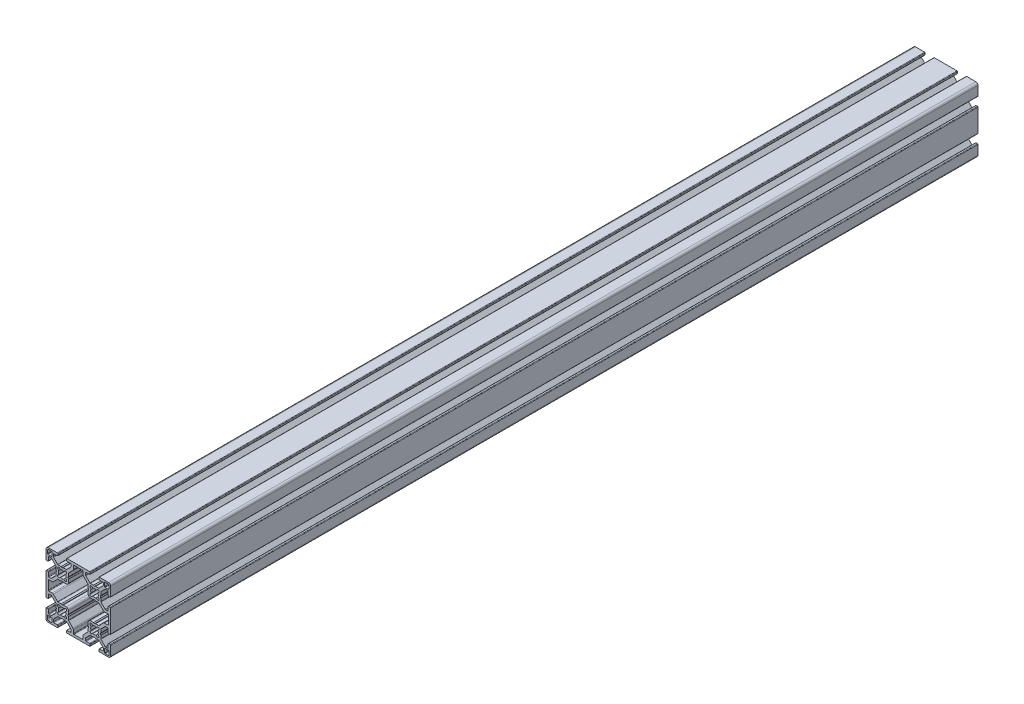
SolidWorks part; units mm, degrees
material "6105-T5 Aluminum"
ref_plane "Front Plane" through (0, 0, 0) normal (0, 0, 1) x (1, 0, 0)
ref_plane "Top Plane" through (0, 0, 0) normal (0, 1, 0) x (1, 0, 0)
ref_plane "Right Plane" through (0, 0, 0) normal (1, 0, 0) x (0, 0, -1)
sketch "Sketch1" plane through (0, 0, 0) normal (0, 0, 1) x (1, 0, 0)
  line L0 (-13.319, -39.4999) -> (-9.88, -39.4999)
  line L1 (-9.5, -39.8799) -> (-9.5, -43.3189)
  line L2 (-9.881, -43.6999) -> (-12.7, -43.6999)
  line L3 (-13.7, -42.6999) -> (-13.7, -39.8809)
  line L4 (39.4999, -43.3189) -> (39.4999, -39.8799)
  line L5 (39.8799, -39.4999) -> (43.3189, -39.4999)
  line L6 (43.6999, -39.8809) -> (43.6999, -42.6999)
  line L7 (42.6999, -43.6999) -> (39.8809, -43.6999)
  line L8 (39.8809, 13.7) -> (42.6999, 13.7)
  line L9 (43.6999, 12.7) -> (43.6999, 9.881)
  line L10 (43.3189, 9.5) -> (39.8799, 9.5)
  line L11 (39.4999, 9.88) -> (39.4999, 13.319)
  line L12 (-9.5, 13.319) -> (-9.5, 9.88)
  line L13 (-9.88, 9.5) -> (-13.319, 9.5)
  line L14 (-13.7, 9.881) -> (-13.7, 12.7)
  line L15 (-12.7, 13.7) -> (-9.881, 13.7)
  line L16 (-1.4942, -3.1981) -> (-2.4733, -3.9799)
  line L17 (-3.9799, -2.4733) -> (-3.1981, -1.4942)
  line L18 (-3.1981, 1.4942) -> (-3.9799, 2.4733)
  line L19 (-2.4733, 3.9799) -> (-1.4942, 3.1981)
  line L20 (1.4942, 3.1981) -> (2.4733, 3.9799)
  line L21 (3.9799, 2.4733) -> (3.1981, 1.4942)
  line L22 (3.1981, -1.4942) -> (3.9799, -2.4733)
  line L23 (2.4733, -3.9799) -> (1.4942, -3.1981)
  line L24 (28.5057, -3.1981) -> (27.5266, -3.9799)
  line L25 (26.02, -2.4733) -> (26.8018, -1.4942)
  line L26 (26.8018, 1.4942) -> (26.02, 2.4733)
  line L27 (27.5266, 3.9799) -> (28.5057, 3.1981)
  line L28 (31.4942, 3.1981) -> (32.4733, 3.9799)
  line L29 (33.9799, 2.4733) -> (33.1981, 1.4942)
  line L30 (33.1981, -1.4942) -> (33.9799, -2.4733)
  line L31 (32.4733, -3.9799) -> (31.4942, -3.1981)
  line L32 (-1.4942, -33.1981) -> (-2.4733, -33.9799)
  line L33 (-3.9799, -32.4733) -> (-3.1981, -31.4942)
  line L34 (-3.1981, -28.5057) -> (-3.9799, -27.5266)
  line L35 (-2.4733, -26.02) -> (-1.4942, -26.8018)
  line L36 (1.4942, -26.8018) -> (2.4733, -26.02)
  line L37 (3.9799, -27.5266) -> (3.1981, -28.5057)
  line L38 (3.1981, -31.4942) -> (3.9799, -32.4733)
  line L39 (2.4733, -33.9799) -> (1.4942, -33.1981)
  line L40 (28.5057, -33.1981) -> (27.5266, -33.9799)
  line L41 (26.02, -32.4733) -> (26.8018, -31.4942)
  line L42 (26.8018, -28.5057) -> (26.02, -27.5266)
  line L43 (27.5266, -26.02) -> (28.5057, -26.8018)
  line L44 (31.4942, -26.8018) -> (32.4733, -26.02)
  line L45 (33.9799, -27.5266) -> (33.1981, -28.5057)
  line L46 (33.1981, -31.4942) -> (33.9799, -32.4733)
  line L47 (32.4733, -33.9799) -> (31.4942, -33.1981)
  line L48 (42.7999, -10.95) -> (42.7999, -19.05)
  line L49 (42.2999, -19.55) -> (39.2681, -19.55)
  line L50 (38.2075, -19.9893) -> (34.178, -24.0188)
  line L51 (33.8244, -24.1653) -> (30.9499, -24.1653)
  line L52 (30.9499, -24.1653) -> (29.9999, -24.6753)
  line L53 (29.9999, -24.6753) -> (29.0499, -24.1653)
  line L54 (29.0499, -24.1653) -> (26.1653, -24.1653)
  line L55 (24.1653, -26.1653) -> (24.1653, -29.1124)
  line L56 (24.1653, -29.1124) -> (24.6753, -30.0624)
  line L57 (24.6753, -30.0624) -> (24.1653, -31.0124)
  line L58 (24.1653, -31.0124) -> (24.1653, -33.8244)
  line L59 (24.0188, -34.178) -> (19.9893, -38.2075)
  line L60 (19.55, -39.2681) -> (19.55, -42.2999)
  line L61 (19.05, -42.7999) -> (10.95, -42.7999)
  line L62 (10.45, -42.2999) -> (10.45, -39.2681)
  line L63 (10.0106, -38.2075) -> (5.9811, -34.178)
  line L64 (5.8347, -33.8244) -> (5.8347, -31.0124)
  line L65 (5.8347, -31.0124) -> (5.3247, -30.0624)
  line L66 (5.3247, -30.0624) -> (5.8347, -29.1124)
  line L67 (5.8347, -29.1124) -> (5.8347, -26.1653)
  line L68 (3.8347, -24.1653) -> (0.95, -24.1653)
  line L69 (0.95, -24.1653) -> (0, -24.6753)
  line L70 (0, -24.6753) -> (-0.95, -24.1653)
  line L71 (-0.95, -24.1653) -> (-3.8245, -24.1653)
  line L72 (-4.178, -24.0188) -> (-8.2075, -19.9893)
  line L73 (-9.2682, -19.55) -> (-12.3, -19.55)
  line L74 (-12.8, -19.05) -> (-12.8, -10.95)
  line L75 (-12.3, -10.45) -> (-9.2682, -10.45)
  line L76 (-8.2075, -10.0106) -> (-4.178, -5.9811)
  line L77 (-3.8245, -5.8347) -> (-0.95, -5.8347)
  line L78 (-0.95, -5.8347) -> (0, -5.3247)
  line L79 (0, -5.3247) -> (0.95, -5.8347)
  line L80 (0.95, -5.8347) -> (3.8347, -5.8347)
  line L81 (5.8347, -3.8347) -> (5.8347, -1.0125)
  line L82 (5.8347, -1.0125) -> (5.3247, -0.0625)
  line L83 (5.3247, -0.0625) -> (5.8347, 0.8875)
  line L84 (5.8347, 0.8875) -> (5.8347, 3.8245)
  line L85 (5.9811, 4.178) -> (10.0106, 8.2075)
  line L86 (10.45, 9.2682) -> (10.45, 12.3)
  line L87 (10.95, 12.8) -> (19.05, 12.8)
  line L88 (19.55, 12.3) -> (19.55, 9.2682)
  line L89 (19.9893, 8.2075) -> (24.0188, 4.178)
  line L90 (24.1653, 3.8245) -> (24.1653, 0.8875)
  line L91 (24.1653, 0.8875) -> (24.6753, -0.0625)
  line L92 (24.6753, -0.0625) -> (24.1653, -1.0125)
  line L93 (24.1653, -1.0125) -> (24.1653, -3.8347)
  line L94 (26.1653, -5.8347) -> (29.0499, -5.8347)
  line L95 (29.0499, -5.8347) -> (29.9999, -5.3247)
  line L96 (29.9999, -5.3247) -> (30.9499, -5.8347)
  line L97 (30.9499, -5.8347) -> (33.8244, -5.8347)
  line L98 (34.178, -5.9811) -> (38.2075, -10.0106)
  line L99 (39.2681, -10.45) -> (42.2999, -10.45)
  line L100 (-14.5, -25.9999) -> (-13.2425, -25.9999)
  line L101 (-12.7425, -25.4999) -> (-12.7425, -22.2674)
  line L102 (-12.2428, -21.75) -> (-10.2602, -21.75)
  line L103 (-9.9067, -21.8964) -> (-5.9811, -25.8219)
  line L104 (-5.8347, -26.1755) -> (-5.8347, -29.1124)
  line L105 (-5.8347, -29.1124) -> (-5.3247, -30.0624)
  line L106 (-5.3247, -30.0624) -> (-5.8347, -31.0124)
  line L107 (-5.8347, -31.0124) -> (-5.8347, -33.8244)
  line L108 (-5.9811, -34.178) -> (-9.9067, -38.1035)
  line L109 (-10.2602, -38.2499) -> (-12.2428, -38.2499)
  line L110 (-12.7425, -37.7325) -> (-12.7425, -34.4999)
  line L111 (-13.2425, -33.9999) -> (-14.5, -33.9999)
  line L112 (-15, -34.4999) -> (-15, -42.9999)
  line L113 (-13, -44.9999) -> (-4.5, -44.9999)
  line L114 (-4, -44.4999) -> (-4, -43.2424)
  line L115 (-4.5, -42.7424) -> (-7.7325, -42.7424)
  line L116 (-8.25, -42.2427) -> (-8.25, -40.2601)
  line L117 (-8.1035, -39.9066) -> (-4.178, -35.9811)
  line L118 (-3.8245, -35.8346) -> (-0.95, -35.8346)
  line L119 (-0.95, -35.8346) -> (0, -35.3246)
  line L120 (0, -35.3246) -> (0.95, -35.8346)
  line L121 (0.95, -35.8346) -> (3.8245, -35.8346)
  line L122 (4.178, -35.9811) -> (8.1035, -39.9066)
  line L123 (8.25, -40.2601) -> (8.25, -42.2427)
  line L124 (7.7325, -42.7424) -> (4.5, -42.7424)
  line L125 (4, -43.2424) -> (4, -44.4999)
  line L126 (4.5, -44.9999) -> (25.4999, -44.9999)
  line L127 (25.9999, -44.4999) -> (25.9999, -43.2424)
  line L128 (25.4999, -42.7424) -> (22.2674, -42.7424)
  line L129 (21.75, -42.2427) -> (21.75, -40.2601)
  line L130 (21.8964, -39.9066) -> (25.8219, -35.9811)
  line L131 (26.1755, -35.8346) -> (29.0499, -35.8346)
  line L132 (29.0499, -35.8346) -> (29.9999, -35.3246)
  line L133 (29.9999, -35.3246) -> (30.9499, -35.8346)
  line L134 (30.9499, -35.8346) -> (33.8244, -35.8346)
  line L135 (34.178, -35.9811) -> (38.1035, -39.9066)
  line L136 (38.2499, -40.2601) -> (38.2499, -42.2427)
  line L137 (37.7325, -42.7424) -> (34.4999, -42.7424)
  line L138 (33.9999, -43.2424) -> (33.9999, -44.4999)
  line L139 (34.4999, -44.9999) -> (42.9999, -44.9999)
  line L140 (44.9999, -42.9999) -> (44.9999, -34.4999)
  line L141 (44.4999, -33.9999) -> (43.2424, -33.9999)
  line L142 (42.7424, -34.4999) -> (42.7424, -37.7325)
  line L143 (42.2427, -38.2499) -> (40.2601, -38.2499)
  line L144 (39.9066, -38.1035) -> (35.9811, -34.178)
  line L145 (35.8346, -33.8244) -> (35.8346, -31.0124)
  line L146 (35.8346, -31.0124) -> (35.3246, -30.0624)
  line L147 (35.3246, -30.0624) -> (35.8346, -29.1124)
  line L148 (35.8346, -29.1124) -> (35.8346, -26.1755)
  line L149 (35.9811, -25.8219) -> (39.9066, -21.8964)
  line L150 (40.2601, -21.75) -> (42.2427, -21.75)
  line L151 (42.7424, -22.2674) -> (42.7424, -25.4999)
  line L152 (43.2424, -25.9999) -> (44.4999, -25.9999)
  line L153 (44.9999, -25.4999) -> (44.9999, -4.5)
  line L154 (44.4999, -4) -> (43.2424, -4)
  line L155 (42.7424, -4.5) -> (42.7424, -7.7325)
  line L156 (42.2427, -8.25) -> (40.2601, -8.25)
  line L157 (39.9066, -8.1035) -> (35.9811, -4.178)
  line L158 (35.8346, -3.8245) -> (35.8346, -1.0125)
  line L159 (35.8346, -1.0125) -> (35.3246, -0.0625)
  line L160 (35.3246, -0.0625) -> (35.8346, 0.8875)
  line L161 (35.8346, 0.8875) -> (35.8346, 3.8245)
  line L162 (35.9811, 4.178) -> (39.9066, 8.1035)
  line L163 (40.2601, 8.25) -> (42.2427, 8.25)
  line L164 (42.7424, 7.7325) -> (42.7424, 4.5)
  line L165 (43.2424, 4) -> (44.4999, 4)
  line L166 (44.9999, 4.5) -> (44.9999, 13)
  line L167 (42.9999, 15) -> (34.4999, 15)
  line L168 (33.9999, 14.5) -> (33.9999, 13.2425)
  line L169 (34.4999, 12.7425) -> (37.7325, 12.7425)
  line L170 (38.2499, 12.2428) -> (38.2499, 10.2602)
  line L171 (38.1035, 9.9067) -> (34.178, 5.9811)
  line L172 (33.8244, 5.8347) -> (30.9499, 5.8347)
  line L173 (30.9499, 5.8347) -> (29.9999, 5.3247)
  line L174 (29.9999, 5.3247) -> (29.0499, 5.8347)
  line L175 (29.0499, 5.8347) -> (26.1755, 5.8347)
  line L176 (25.8219, 5.9811) -> (21.8964, 9.9067)
  line L177 (21.75, 10.2602) -> (21.75, 12.2428)
  line L178 (22.2674, 12.7425) -> (25.4999, 12.7425)
  line L179 (25.9999, 13.2425) -> (25.9999, 14.5)
  line L180 (25.4999, 15) -> (4.5, 15)
  line L181 (4, 14.5) -> (4, 13.2425)
  line L182 (4.5, 12.7425) -> (7.7325, 12.7425)
  line L183 (8.25, 12.2428) -> (8.25, 10.2602)
  line L184 (8.1035, 9.9067) -> (4.178, 5.9811)
  line L185 (3.8245, 5.8347) -> (0.95, 5.8347)
  line L186 (0.95, 5.8347) -> (0, 5.3247)
  line L187 (0, 5.3247) -> (-0.95, 5.8347)
  line L188 (-0.95, 5.8347) -> (-3.8245, 5.8347)
  line L189 (-4.178, 5.9811) -> (-8.1035, 9.9067)
  line L190 (-8.25, 10.2602) -> (-8.25, 12.2428)
  line L191 (-7.7325, 12.7425) -> (-4.5, 12.7425)
  line L192 (-4, 13.2425) -> (-4, 14.5)
  line L193 (-4.5, 15) -> (-13, 15)
  line L194 (-15, 13) -> (-15, 4.5)
  line L195 (-14.5, 4) -> (-13.2425, 4)
  line L196 (-12.7425, 4.5) -> (-12.7425, 7.7325)
  line L197 (-12.2428, 8.25) -> (-10.2602, 8.25)
  line L198 (-9.9067, 8.1035) -> (-5.9811, 4.178)
  line L199 (-5.8347, 3.8245) -> (-5.8347, 0.8875)
  line L200 (-5.8347, 0.8875) -> (-5.3247, -0.0625)
  line L201 (-5.3247, -0.0625) -> (-5.8347, -1.0125)
  line L202 (-5.8347, -1.0125) -> (-5.8347, -3.8245)
  line L203 (-5.9811, -4.178) -> (-9.9067, -8.1035)
  line L204 (-10.2602, -8.25) -> (-12.2428, -8.25)
  line L205 (-12.7425, -7.7325) -> (-12.7425, -4.5)
  line L206 (-13.2425, -4) -> (-14.5, -4)
  line L207 (-15, -4.5) -> (-15, -25.4999)
  arc A0 (-13.319, -39.4999) -> (-13.7, -39.8809) centre (-13.319, -39.8809) ccw
  arc A1 (-9.5, -39.8799) -> (-9.88, -39.4999) centre (-9.88, -39.8799) ccw
  arc A2 (-9.881, -43.6999) -> (-9.5, -43.3189) centre (-9.881, -43.3189) ccw
  arc A3 (-13.7, -42.6999) -> (-12.7, -43.6999) centre (-12.7, -42.6999) ccw
  arc A4 (39.4999, -43.3189) -> (39.8809, -43.6999) centre (39.8809, -43.3189) ccw
  arc A5 (39.8799, -39.4999) -> (39.4999, -39.8799) centre (39.8799, -39.8799) ccw
  arc A6 (43.6999, -39.8809) -> (43.3189, -39.4999) centre (43.3189, -39.8809) ccw
  arc A7 (42.6999, -43.6999) -> (43.6999, -42.6999) centre (42.6999, -42.6999) ccw
  arc A8 (39.8809, 13.7) -> (39.4999, 13.319) centre (39.8809, 13.319) ccw
  arc A9 (43.6999, 12.7) -> (42.6999, 13.7) centre (42.6999, 12.7) ccw
  arc A10 (43.3189, 9.5) -> (43.6999, 9.881) centre (43.3189, 9.881) ccw
  arc A11 (39.4999, 9.88) -> (39.8799, 9.5) centre (39.8799, 9.88) ccw
  arc A12 (-9.5, 13.319) -> (-9.881, 13.7) centre (-9.881, 13.319) ccw
  arc A13 (-9.88, 9.5) -> (-9.5, 9.88) centre (-9.88, 9.88) ccw
  arc A14 (-13.7, 9.881) -> (-13.319, 9.5) centre (-13.319, 9.881) ccw
  arc A15 (-12.7, 13.7) -> (-13.7, 12.7) centre (-12.7, 12.7) ccw
  arc A16 (-1.4942, -3.1981) -> (1.4942, -3.1981) centre (0, 0) ccw
  arc A17 (-3.9799, -2.4733) -> (-2.4733, -3.9799) centre (-3.1422, -3.1422) ccw
  arc A18 (-3.1981, 1.4942) -> (-3.1981, -1.4942) centre (0, 0) ccw
  arc A19 (-2.4733, 3.9799) -> (-3.9799, 2.4733) centre (-3.1422, 3.1422) ccw
  arc A20 (1.4942, 3.1981) -> (-1.4942, 3.1981) centre (0, 0) ccw
  arc A21 (3.9799, 2.4733) -> (2.4733, 3.9799) centre (3.1422, 3.1422) ccw
  arc A22 (3.1981, -1.4942) -> (3.1981, 1.4942) centre (0, 0) ccw
  arc A23 (2.4733, -3.9799) -> (3.9799, -2.4733) centre (3.1422, -3.1422) ccw
  arc A24 (28.5057, -3.1981) -> (31.4942, -3.1981) centre (29.9999, 0) ccw
  arc A25 (26.02, -2.4733) -> (27.5266, -3.9799) centre (26.8577, -3.1422) ccw
  arc A26 (26.8018, 1.4942) -> (26.8018, -1.4942) centre (29.9999, 0) ccw
  arc A27 (27.5266, 3.9799) -> (26.02, 2.4733) centre (26.8577, 3.1422) ccw
  arc A28 (31.4942, 3.1981) -> (28.5057, 3.1981) centre (29.9999, 0) ccw
  arc A29 (33.9799, 2.4733) -> (32.4733, 3.9799) centre (33.1422, 3.1422) ccw
  arc A30 (33.1981, -1.4942) -> (33.1981, 1.4942) centre (29.9999, 0) ccw
  arc A31 (32.4733, -3.9799) -> (33.9799, -2.4733) centre (33.1422, -3.1422) ccw
  arc A32 (-1.4942, -33.1981) -> (1.4942, -33.1981) centre (0, -29.9999) ccw
  arc A33 (-3.9799, -32.4733) -> (-2.4733, -33.9799) centre (-3.1422, -33.1422) ccw
  arc A34 (-3.1981, -28.5057) -> (-3.1981, -31.4942) centre (0, -29.9999) ccw
  arc A35 (-2.4733, -26.02) -> (-3.9799, -27.5266) centre (-3.1422, -26.8577) ccw
  arc A36 (1.4942, -26.8018) -> (-1.4942, -26.8018) centre (0, -29.9999) ccw
  arc A37 (3.9799, -27.5266) -> (2.4733, -26.02) centre (3.1422, -26.8577) ccw
  arc A38 (3.1981, -31.4942) -> (3.1981, -28.5057) centre (0, -29.9999) ccw
  arc A39 (2.4733, -33.9799) -> (3.9799, -32.4733) centre (3.1422, -33.1422) ccw
  arc A40 (28.5057, -33.1981) -> (31.4942, -33.1981) centre (29.9999, -29.9999) ccw
  arc A41 (26.02, -32.4733) -> (27.5266, -33.9799) centre (26.8577, -33.1422) ccw
  arc A42 (26.8018, -28.5057) -> (26.8018, -31.4942) centre (29.9999, -29.9999) ccw
  arc A43 (27.5266, -26.02) -> (26.02, -27.5266) centre (26.8577, -26.8577) ccw
  arc A44 (31.4942, -26.8018) -> (28.5057, -26.8018) centre (29.9999, -29.9999) ccw
  arc A45 (33.9799, -27.5266) -> (32.4733, -26.02) centre (33.1422, -26.8577) ccw
  arc A46 (33.1981, -31.4942) -> (33.1981, -28.5057) centre (29.9999, -29.9999) ccw
  arc A47 (32.4733, -33.9799) -> (33.9799, -32.4733) centre (33.1422, -33.1422) ccw
  arc A48 (42.7999, -10.95) -> (42.2999, -10.45) centre (42.2999, -10.95) ccw
  arc A49 (42.2999, -19.55) -> (42.7999, -19.05) centre (42.2999, -19.05) ccw
  arc A50 (39.2681, -19.55) -> (38.2075, -19.9893) centre (39.2681, -21.05) ccw
  arc A51 (33.8244, -24.1653) -> (34.178, -24.0188) centre (33.8244, -23.6653) ccw
  arc A52 (26.1653, -24.1653) -> (24.1653, -26.1653) centre (26.1653, -26.1653) ccw
  arc A53 (24.0188, -34.178) -> (24.1653, -33.8244) centre (23.6653, -33.8244) ccw
  arc A54 (19.9893, -38.2075) -> (19.55, -39.2681) centre (21.05, -39.2681) ccw
  arc A55 (19.05, -42.7999) -> (19.55, -42.2999) centre (19.05, -42.2999) ccw
  arc A56 (10.45, -42.2999) -> (10.95, -42.7999) centre (10.95, -42.2999) ccw
  arc A57 (10.45, -39.2681) -> (10.0106, -38.2075) centre (8.95, -39.2681) ccw
  arc A58 (5.8347, -33.8244) -> (5.9811, -34.178) centre (6.3347, -33.8244) ccw
  arc A59 (5.8347, -26.1653) -> (3.8347, -24.1653) centre (3.8347, -26.1653) ccw
  arc A60 (-4.178, -24.0188) -> (-3.8245, -24.1653) centre (-3.8245, -23.6653) ccw
  arc A61 (-8.2075, -19.9893) -> (-9.2682, -19.55) centre (-9.2682, -21.05) ccw
  arc A62 (-12.8, -19.05) -> (-12.3, -19.55) centre (-12.3, -19.05) ccw
  arc A63 (-12.3, -10.45) -> (-12.8, -10.95) centre (-12.3, -10.95) ccw
  arc A64 (-9.2682, -10.45) -> (-8.2075, -10.0106) centre (-9.2682, -8.95) ccw
  arc A65 (-3.8245, -5.8347) -> (-4.178, -5.9811) centre (-3.8245, -6.3347) ccw
  arc A66 (3.8347, -5.8347) -> (5.8347, -3.8347) centre (3.8347, -3.8347) ccw
  arc A67 (5.9811, 4.178) -> (5.8347, 3.8245) centre (6.3347, 3.8245) ccw
  arc A68 (10.0106, 8.2075) -> (10.45, 9.2682) centre (8.95, 9.2682) ccw
  arc A69 (10.95, 12.8) -> (10.45, 12.3) centre (10.95, 12.3) ccw
  arc A70 (19.55, 12.3) -> (19.05, 12.8) centre (19.05, 12.3) ccw
  arc A71 (19.55, 9.2682) -> (19.9893, 8.2075) centre (21.05, 9.2682) ccw
  arc A72 (24.1653, 3.8245) -> (24.0188, 4.178) centre (23.6653, 3.8245) ccw
  arc A73 (24.1653, -3.8347) -> (26.1653, -5.8347) centre (26.1653, -3.8347) ccw
  arc A74 (34.178, -5.9811) -> (33.8244, -5.8347) centre (33.8244, -6.3347) ccw
  arc A75 (38.2075, -10.0106) -> (39.2681, -10.45) centre (39.2681, -8.95) ccw
  arc A76 (-13.2425, -25.9999) -> (-12.7425, -25.4999) centre (-13.2425, -25.4999) ccw
  arc A77 (-12.2428, -21.75) -> (-12.7425, -22.2674) centre (-12.2428, -22.25) ccw
  arc A78 (-9.9067, -21.8964) -> (-10.2602, -21.75) centre (-10.2602, -22.25) ccw
  arc A79 (-5.8347, -26.1755) -> (-5.9811, -25.8219) centre (-6.3347, -26.1755) ccw
  arc A80 (-5.9811, -34.178) -> (-5.8347, -33.8244) centre (-6.3347, -33.8244) ccw
  arc A81 (-10.2602, -38.2499) -> (-9.9067, -38.1035) centre (-10.2602, -37.7499) ccw
  arc A82 (-12.7425, -37.7325) -> (-12.2428, -38.2499) centre (-12.2428, -37.7499) ccw
  arc A83 (-12.7425, -34.4999) -> (-13.2425, -33.9999) centre (-13.2425, -34.4999) ccw
  arc A84 (-14.5, -33.9999) -> (-15, -34.4999) centre (-14.5, -34.4999) ccw
  arc A85 (-15, -42.9999) -> (-13, -44.9999) centre (-13, -42.9999) ccw
  arc A86 (-4.5, -44.9999) -> (-4, -44.4999) centre (-4.5, -44.4999) ccw
  arc A87 (-4, -43.2424) -> (-4.5, -42.7424) centre (-4.5, -43.2424) ccw
  arc A88 (-8.25, -42.2427) -> (-7.7325, -42.7424) centre (-7.75, -42.2427) ccw
  arc A89 (-8.1035, -39.9066) -> (-8.25, -40.2601) centre (-7.75, -40.2601) ccw
  arc A90 (-3.8245, -35.8346) -> (-4.178, -35.9811) centre (-3.8245, -36.3346) ccw
  arc A91 (4.178, -35.9811) -> (3.8245, -35.8346) centre (3.8245, -36.3346) ccw
  arc A92 (8.25, -40.2601) -> (8.1035, -39.9066) centre (7.75, -40.2601) ccw
  arc A93 (7.7325, -42.7424) -> (8.25, -42.2427) centre (7.75, -42.2427) ccw
  arc A94 (4.5, -42.7424) -> (4, -43.2424) centre (4.5, -43.2424) ccw
  arc A95 (4, -44.4999) -> (4.5, -44.9999) centre (4.5, -44.4999) ccw
  arc A96 (25.4999, -44.9999) -> (25.9999, -44.4999) centre (25.4999, -44.4999) ccw
  arc A97 (25.9999, -43.2424) -> (25.4999, -42.7424) centre (25.4999, -43.2424) ccw
  arc A98 (21.75, -42.2427) -> (22.2674, -42.7424) centre (22.25, -42.2427) ccw
  arc A99 (21.8964, -39.9066) -> (21.75, -40.2601) centre (22.25, -40.2601) ccw
  arc A100 (26.1755, -35.8346) -> (25.8219, -35.9811) centre (26.1755, -36.3346) ccw
  arc A101 (34.178, -35.9811) -> (33.8244, -35.8346) centre (33.8244, -36.3346) ccw
  arc A102 (38.2499, -40.2601) -> (38.1035, -39.9066) centre (37.7499, -40.2601) ccw
  arc A103 (37.7325, -42.7424) -> (38.2499, -42.2427) centre (37.7499, -42.2427) ccw
  arc A104 (34.4999, -42.7424) -> (33.9999, -43.2424) centre (34.4999, -43.2424) ccw
  arc A105 (33.9999, -44.4999) -> (34.4999, -44.9999) centre (34.4999, -44.4999) ccw
  arc A106 (42.9999, -44.9999) -> (44.9999, -42.9999) centre (42.9999, -42.9999) ccw
  arc A107 (44.9999, -34.4999) -> (44.4999, -33.9999) centre (44.4999, -34.4999) ccw
  arc A108 (43.2424, -33.9999) -> (42.7424, -34.4999) centre (43.2424, -34.4999) ccw
  arc A109 (42.2427, -38.2499) -> (42.7424, -37.7325) centre (42.2427, -37.7499) ccw
  arc A110 (39.9066, -38.1035) -> (40.2601, -38.2499) centre (40.2601, -37.7499) ccw
  arc A111 (35.8346, -33.8244) -> (35.9811, -34.178) centre (36.3346, -33.8244) ccw
  arc A112 (35.9811, -25.8219) -> (35.8346, -26.1755) centre (36.3346, -26.1755) ccw
  arc A113 (40.2601, -21.75) -> (39.9066, -21.8964) centre (40.2601, -22.25) ccw
  arc A114 (42.7424, -22.2674) -> (42.2427, -21.75) centre (42.2427, -22.25) ccw
  arc A115 (42.7424, -25.4999) -> (43.2424, -25.9999) centre (43.2424, -25.4999) ccw
  arc A116 (44.4999, -25.9999) -> (44.9999, -25.4999) centre (44.4999, -25.4999) ccw
  arc A117 (44.9999, -4.5) -> (44.4999, -4) centre (44.4999, -4.5) ccw
  arc A118 (43.2424, -4) -> (42.7424, -4.5) centre (43.2424, -4.5) ccw
  arc A119 (42.2427, -8.25) -> (42.7424, -7.7325) centre (42.2427, -7.75) ccw
  arc A120 (39.9066, -8.1035) -> (40.2601, -8.25) centre (40.2601, -7.75) ccw
  arc A121 (35.8346, -3.8245) -> (35.9811, -4.178) centre (36.3346, -3.8245) ccw
  arc A122 (35.9811, 4.178) -> (35.8346, 3.8245) centre (36.3346, 3.8245) ccw
  arc A123 (40.2601, 8.25) -> (39.9066, 8.1035) centre (40.2601, 7.75) ccw
  arc A124 (42.7424, 7.7325) -> (42.2427, 8.25) centre (42.2427, 7.75) ccw
  arc A125 (42.7424, 4.5) -> (43.2424, 4) centre (43.2424, 4.5) ccw
  arc A126 (44.4999, 4) -> (44.9999, 4.5) centre (44.4999, 4.5) ccw
  arc A127 (44.9999, 13) -> (42.9999, 15) centre (42.9999, 13) ccw
  arc A128 (34.4999, 15) -> (33.9999, 14.5) centre (34.4999, 14.5) ccw
  arc A129 (33.9999, 13.2425) -> (34.4999, 12.7425) centre (34.4999, 13.2425) ccw
  arc A130 (38.2499, 12.2428) -> (37.7325, 12.7425) centre (37.7499, 12.2428) ccw
  arc A131 (38.1035, 9.9067) -> (38.2499, 10.2602) centre (37.7499, 10.2602) ccw
  arc A132 (33.8244, 5.8347) -> (34.178, 5.9811) centre (33.8244, 6.3347) ccw
  arc A133 (25.8219, 5.9811) -> (26.1755, 5.8347) centre (26.1755, 6.3347) ccw
  arc A134 (21.75, 10.2602) -> (21.8964, 9.9067) centre (22.25, 10.2602) ccw
  arc A135 (22.2674, 12.7425) -> (21.75, 12.2428) centre (22.25, 12.2428) ccw
  arc A136 (25.4999, 12.7425) -> (25.9999, 13.2425) centre (25.4999, 13.2425) ccw
  arc A137 (25.9999, 14.5) -> (25.4999, 15) centre (25.4999, 14.5) ccw
  arc A138 (4.5, 15) -> (4, 14.5) centre (4.5, 14.5) ccw
  arc A139 (4, 13.2425) -> (4.5, 12.7425) centre (4.5, 13.2425) ccw
  arc A140 (8.25, 12.2428) -> (7.7325, 12.7425) centre (7.75, 12.2428) ccw
  arc A141 (8.1035, 9.9067) -> (8.25, 10.2602) centre (7.75, 10.2602) ccw
  arc A142 (3.8245, 5.8347) -> (4.178, 5.9811) centre (3.8245, 6.3347) ccw
  arc A143 (-4.178, 5.9811) -> (-3.8245, 5.8347) centre (-3.8245, 6.3347) ccw
  arc A144 (-8.25, 10.2602) -> (-8.1035, 9.9067) centre (-7.75, 10.2602) ccw
  arc A145 (-7.7325, 12.7425) -> (-8.25, 12.2428) centre (-7.75, 12.2428) ccw
  arc A146 (-4.5, 12.7425) -> (-4, 13.2425) centre (-4.5, 13.2425) ccw
  arc A147 (-4, 14.5) -> (-4.5, 15) centre (-4.5, 14.5) ccw
  arc A148 (-13, 15) -> (-15, 13) centre (-13, 13) ccw
  arc A149 (-15, 4.5) -> (-14.5, 4) centre (-14.5, 4.5) ccw
  arc A150 (-13.2425, 4) -> (-12.7425, 4.5) centre (-13.2425, 4.5) ccw
  arc A151 (-12.2428, 8.25) -> (-12.7425, 7.7325) centre (-12.2428, 7.75) ccw
  arc A152 (-9.9067, 8.1035) -> (-10.2602, 8.25) centre (-10.2602, 7.75) ccw
  arc A153 (-5.8347, 3.8245) -> (-5.9811, 4.178) centre (-6.3347, 3.8245) ccw
  arc A154 (-5.9811, -4.178) -> (-5.8347, -3.8245) centre (-6.3347, -3.8245) ccw
  arc A155 (-10.2602, -8.25) -> (-9.9067, -8.1035) centre (-10.2602, -7.75) ccw
  arc A156 (-12.7425, -7.7325) -> (-12.2428, -8.25) centre (-12.2428, -7.75) ccw
  arc A157 (-12.7425, -4.5) -> (-13.2425, -4) centre (-13.2425, -4.5) ccw
  arc A158 (-14.5, -4) -> (-15, -4.5) centre (-14.5, -4.5) ccw
  arc A159 (-15, -25.4999) -> (-14.5, -25.9999) centre (-14.5, -25.4999) ccw
extrude "Extrude1" add sketch "Sketch1" against normal blind 805
sketch "Sketch2" plane through (0, 15, 0) normal (0, 1, 0) x (1, 0, 0)
  line L0 (0, 805) -> (0, 0) construction
  line L1 (-4.5, 805) -> (-13, 805) construction
  circle A0 centre (0, 65) radius 3.175
  circle A1 centre (0, 790) radius 3.175
  circle A2 centre (0, 760) radius 3.175
  circle A3 centre (0, 595) radius 3.175
  point P12 (-8.75, 805)
  dimension "D1" = 6.35
  dimension "D2" = 30
  dimension "D3" = 15
  dimension "D4" = 65
  dimension "D5" = 210
extrude "Cut-Extrude1" cut sketch "Sketch2" against normal through all
sketch "Sketch3" plane through (-15, 0, 0) normal (-1, 0, 0) x (0, 0, 1)
  line L0 (-805, 13) -> (-805, 4.5) construction
  line L1 (-805, -0.0625) -> (0, -0.0625) construction
  circle A0 centre (-790, -0.0625) radius 3.175
  circle A1 centre (-760, -0.0625) radius 3.175
  circle A2 centre (-595, -0.0625) radius 3.175
  circle A3 centre (-65, -0.0625) radius 3.175
  dimension "D1" = 6.35
  dimension "D2" = 65
  dimension "D3" = 15
  dimension "D4" = 30
  dimension "D5" = 210
extrude "Cut-Extrude2" cut sketch "Sketch3" against normal through all
